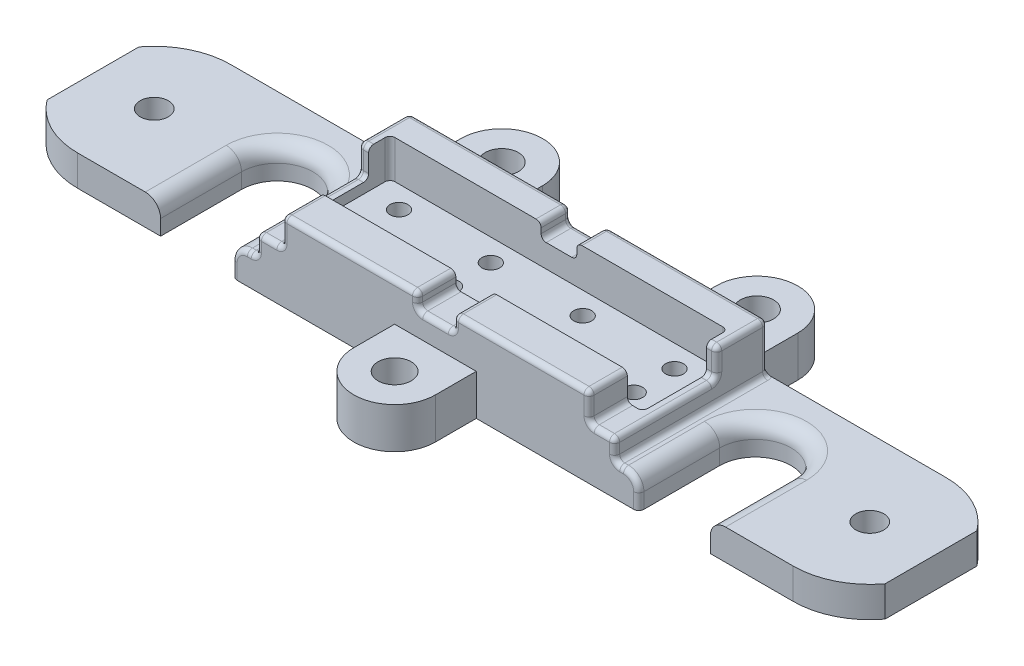
SolidWorks part; units mm, degrees
material "Delrin 2700 NC010, Low Viscosity Acetal Copolymer (SS)"
ref_plane "Front Plane" through (0, 0, 0) normal (0, 0, 1) x (1, 0, 0)
ref_plane "Top Plane" through (0, 0, 0) normal (0, 1, 0) x (1, 0, 0)
ref_plane "Right Plane" through (0, 0, 0) normal (1, 0, 0) x (0, 0, -1)
sketch "Sketch1" plane through (0, 0, 0) normal (0, 1, 0) x (1, 0, 0)
  line L1 (-35.1, -15) -> (0, -15)
  line L2 (-35.1, -15) -> (-35.1, 15)
  line L3 (-35.1, 15) -> (0, 15)
  line L4 (0, -15) -> (0, 15)
  line L5 (-35.1, -15) -> (0, 15) construction
  line L6 (-35.1, 15) -> (0, -15) construction
  point P0 (-17.55, 0)
  point P8 (0, 0)
  dimension "D1" = 35.1
  dimension "D2" = 30
extrude "Boss-Extrude1" add sketch "Sketch1" along normal blind 15.5
shell "Shell1" [suppressed] thickness 1
sketch "Sketch7" plane through (0, 15.5, 0) normal (0, 1, 0) x (1, 0, 0)
  line L0 (0, -15) -> (0, 15) construction
  line L1 (0, -7.5) -> (-33.1, -7.5)
  line L2 (0, -7.5) -> (0, 9.2)
  line L3 (0, 9.2) -> (-33.1, 9.2)
  line L4 (-33.1, -7.5) -> (-33.1, 9.2)
  line L5 (-35.1, -15) -> (0, -15) construction
  line L6 (0, 15) -> (-35.1, 15) construction
  line L7 (-35.1, 15) -> (-35.1, -15) construction
  dimension "D1" = 7.5
  dimension "D2" = 5.8
  dimension "D3" = 2
extrude "Cut-Extrude5" cut sketch "Sketch7" against normal offset from surface (7.5 mm away) 8 up to face at (-17.55, 0, 0)
sketch "Sketch2" plane through (0, 0, 0) normal (0, 1, 0) x (-1, 0, 0)
  line L0 (27, 3.15) -> (9, 3.15) construction
  line L2 (27, 3.15) -> (27, -4.85) construction
  line L3 (27, -4.85) -> (9, -4.85) construction
  line L4 (9, -4.85) -> (9, 3.15) construction
  line L5 (27, -0.85) -> (18.8977, -0.85) construction
  line L6 (17.55, -15) -> (17.55, 15) construction
  line L7 (0, 7.5) -> (0, -9.2) construction
  line L8 (27, -0.85) -> (0, -0.85) construction
  line L9 (0, -15) -> (35.1, -15) construction
  line L10 (35.1, 15) -> (0, 15) construction
  circle A0 centre (27, 3.15) radius 1.75
  circle A1 centre (9, 3.15) radius 1.75
  circle A2 centre (27, -4.85) radius 1.75
  circle A3 centre (9, -4.85) radius 1.75
  circle A5 centre (27, 3.15) radius 2.5 construction
  circle A6 centre (27, -4.85) radius 2.5 construction
  circle A7 centre (9, -4.85) radius 2.5 construction
  circle A8 centre (9, 3.15) radius 2.5 construction
  dimension "D1" = 3.5
  dimension "D4" = 9
  dimension "D5" = 5
  dimension "D2" = 18
  dimension "D3" = 8
extrude "Cut-Extrude1" cut sketch "Sketch2" along normal through all
sketch "Sketch3" [suppressed] plane through (0, 5, 0) normal (0, 1, 0) x (1, 0, 0)
  line L1 (-2.9573, -5.1559) -> (2.9865, -5.139)
  line L2 (2.9865, -5.139) -> (5.9438, 0.0169)
  line L3 (5.9438, 0.0169) -> (2.9573, 5.1559)
  line L4 (2.9573, 5.1559) -> (-2.9865, 5.139)
  line L5 (-2.9865, 5.139) -> (-5.9438, -0.0169)
  line L6 (-5.9438, -0.0169) -> (-2.9573, -5.1559)
  circle A0 centre (0, 0) radius 2.6 construction
  circle A1 centre (0, 0) radius 5.1475 construction
  dimension "D1" = 5.2
extrude "Cut-Extrude2" [suppressed] cut sketch "Sketch3" against normal blind 0.5
sketch "Sketch4" plane through (-35.1, 0, 0) normal (-1, 0, 0) x (0, 0, 1)
  line L0 (-15, 15.5) -> (15, 15.5) construction
  line L1 (-5, 15.5) -> (15, 15.5)
  line L3 (-5, 10) -> (15, 10)
  line L4 (15, 15.5) -> (15, 10)
  line L5 (0, 10) -> (0, 0) construction
  line L11 (-15, 0) -> (15, 0) construction
  line L12 (-5, 10) -> (-5, 15.5)
  dimension "D1" = 5
  dimension "D2" = 5.5
extrude "Cut-Extrude3" cut sketch "Sketch4" against normal offset from surface (5 mm away) 3 up to face at (-33.1, 11.75, -0.85) offset beyond the face yes
sketch "Sketch8" plane through (0, 0, 0) normal (0, -1, 0) x (-1, 0, 0)
  line L0 (35.1, -15) -> (70.1, -15)
  line L1 (35.1, 15) -> (70.1, 15)
  line L2 (35.1, 15) -> (35.1, -15)
  line L3 (82.1, 9) -> (82.1, -9)
  arc A0 (70.1, 15) -> (82.1, 9) centre (70.1, 0) cw
  circle A1 centre (70.1, 0) radius 2.75
  arc A2 (82.1, -9) -> (70.1, -15) centre (70.1, 0) cw
  dimension "D2" = 5.5
  dimension "D1" = 35
  dimension "D3" = 12
extrude "bolt extrude" add sketch "Sketch8" against normal blind 6
mirror "Mirror1" about plane through (0, 0, 0) normal (1, 0, 0) of bodies 112 105
fillet "Fillet3" radius 1 8 edges at (30.1, 10, 11.25) (-30.1, 10, 11.25) (30.1, 15.5, 11.25) (-30.1, 15.5, 11.25) (34.1, 15.5, -5) (34.1, 10, -5) (-34.1, 15.5, -5) (-34.1, 10, -5)
fillet "Fillet5" [suppressed] radius 0.5
sketch "Sketch9" plane through (0, 15.5, 0) normal (0, 1, 0) x (1, 0, 0)
  line L0 (35.1, 15) -> (-35.1, 15) construction
  line L1 (-3.5, 15) -> (3.5, 15)
  line L2 (-3.5, 15) -> (-3.5, -15)
  line L3 (-3.5, -15) -> (3.5, -15)
  line L4 (3.5, 15) -> (3.5, -15)
  line L5 (-29.1, -15) -> (29.1, -15) construction
  dimension "D1" = 3.5
  dimension "D2" = 3.5
extrude "Cut-Extrude6" cut sketch "Sketch9" against normal blind 3
fillet "Fillet6" radius 1 14 edges at (35.1, 10.75, -15) (-35.1, 10.75, -15) (-33.1, 9, 7.5) (-33.1, 11.75, -9.2) (33.1, 11.75, -9.2) (33.1, 9, 7.5) (-3.5, 12.5, -12.1) (3.5, 12.5, -12.1) (3.5, 12.5, 11.25) (-3.5, 12.5, 11.25) (3.5, 15.5, 11.25) (-3.5, 15.5, 11.25) (-3.5, 15.5, -12.1) (3.5, 15.5, -12.1)
fillet "Fillet7" [suppressed] radius 1
fillet "Fillet9" radius 1 25 edges at (-35.1, 10, 5.5) (35.1, 6, 0.5) (34.8071, 6, -14.7071) (35.1, 10, 5.5) (35.1, 10.2929, -4.7071) (35.1, 12.75, -5) (35.1, 15.2071, -5.2929) (35.1, 15.5, -10) (34.8071, 15.5, -14.7071) (19.3, 15.5, -15) (3.7929, 15.2071, -15) (3.5, 14, -15) (3.2071, 12.7929, -15) (0, 12.5, -15) (-3.2071, 12.7929, -15) (-3.5, 14, -15) (-3.7929, 15.2071, -15) (-19.3, 15.5, -15) (-34.8071, 15.5, -14.7071) (-35.1, 15.5, -10) (-35.1, 15.2071, -5.2929) (-35.1, 12.75, -5) (-35.1, 10.2929, -4.7071) (-34.8071, 6, -14.7071) (-35.1, 6, 0.5)
sketch "Sketch11" plane through (0, 0, 0) normal (0, -1, 0) x (1, 0, 0)
  line L0 (70.1, -15) -> (-70.1, -15) construction
  line L1 (-70.1, 15) -> (70.1, 15) construction
  line L2 (70.1, -15) -> (-70.1, -15)
  line L3 (-70.1, 15) -> (70.1, 15)
  line L4 (-70.1, 12) -> (70.1, 12)
  line L5 (70.1, -12) -> (-70.1, -12)
  line L6 (-70.1, 12) -> (-70.1, 15)
  line L7 (-70.1, -15) -> (-70.1, -12)
  line L8 (70.1, 12) -> (70.1, 15)
  line L9 (70.1, -12) -> (70.1, -15)
  point P9 (70.1, 13.5)
  dimension "D1" = 3
extrude "Boss-Extrude3" add sketch "Sketch11" along normal blind 15
sketch "Sketch12" plane through (0, 0, 0) normal (0, -1, 0) x (1, 0, 0)
  line L0 (-8, 15) -> (-8, 23)
  line L1 (17, -15) -> (17, -23)
  line L2 (8, 23) -> (8, 15)
  line L3 (8, 15) -> (-8, 15)
  line L4 (70.1, 15) -> (-70.1, 15) construction
  line L5 (-70.1, -15) -> (70.1, -15) construction
  line L6 (17, -15) -> (33, -15)
  line L7 (33, -15) -> (33, -23)
  line L8 (0, 0) -> (0, 15) construction
  line L9 (-33, -15) -> (-33, -23)
  line L10 (-17, -15) -> (-33, -15)
  line L11 (-17, -15) -> (-17, -23)
  arc A0 (-8, 23) -> (8, 23) centre (0, 23) cw
  circle A1 centre (0, 23) radius 3.25
  arc A2 (33, -23) -> (17, -23) centre (25, -23) cw
  circle A3 centre (25, -23) radius 3.25
  circle A4 centre (-25, -23) radius 3.25
  arc A5 (-33, -23) -> (-17, -23) centre (-25, -23) ccw
  point P6 (0, 15)
  dimension "D1" = 6.5
  dimension "D2" = 8
  dimension "D3" = 8
  dimension "D4" = 25
extrude "Boss-Extrude4" add sketch "Sketch12" against normal blind 8
sketch "Sketch10" plane through (0, 0, 0) normal (0, -1, 0) x (-1, 0, 0)
  line L0 (-39.85, 0.85) -> (-39.85, -15)
  line L1 (70.1, -15) -> (-70.1, -15) construction
  line L2 (-53.85, 0.85) -> (-53.85, -15)
  line L3 (39.85, 0.85) -> (39.85, -15)
  line L4 (53.85, 0.85) -> (53.85, -15)
  line L5 (-53.85, -15) -> (-39.85, -15)
  line L6 (39.85, -15) -> (53.85, -15)
  arc A0 (53.85, 0.85) -> (39.85, 0.85) centre (46.85, 0.85) ccw
  arc A1 (-39.85, 0.85) -> (-53.85, 0.85) centre (-46.85, 0.85) ccw
  dimension "D1" = 14
extrude "Cut-Extrude7" cut sketch "Sketch10" against normal through all and the other way through all
fillet "Fillet10" radius 3 6 edges at (-53.85, 6, 7.075) (-46.85, 6, -7.85) (39.85, 6, 7.075) (46.85, 6, -7.85) (-39.85, 6, 7.075) (53.85, 6, 7.075)
fillet "Fillet11" [suppressed] radius 8
fillet "Fillet12" [suppressed] radius 2
fillet "Fillet13" [suppressed] radius 2
fillet "Fillet14" radius 1 29 edges at (-39.85, -6, 15) (-38.9713, 5.1213, 15) (-36.475, 6, 15) (-35.3929, 6.2929, 15) (-35.1, 8, 15) (-34.8071, 9.7071, 15) (-32.6, 10, 15) (-30.3929, 10.2929, 15) (-30.1, 12.75, 15) (-29.8071, 15.2071, 15) (39.85, -6, 15) (38.9713, 5.1213, 15) (36.475, 6, 15) (35.3929, 6.2929, 15) (35.1, 8, 15) (34.8071, 9.7071, 15) (32.6, 10, 15) (30.3929, 10.2929, 15) (30.1, 12.75, 15) (29.8071, 15.2071, 15) (16.8, 15.5, 15) (3.7929, 15.2071, 15) (3.5, 14, 15) (3.2071, 12.7929, 15) (0, 12.5, 15) (-3.2071, 12.7929, 15) (-3.5, 14, 15) (-3.7929, 15.2071, 15) (-16.8, 15.5, 15)
sketch "Sketch13" plane through (0, 0, 0) normal (0, -1, 0) x (1, 0, 0)
  line L1 (-31, 7.15) -> (31, 7.15)
  line L2 (-31, 7.15) -> (-31, -8.85)
  line L3 (-31, -8.85) -> (31, -8.85)
  line L4 (31, 7.15) -> (31, -8.85)
  circle A0 centre (9, 3.15) radius 1.75 construction
  circle A1 centre (9, -4.85) radius 1.75 construction
  circle A2 centre (27, 3.15) radius 1.75 construction
  circle A3 centre (-27, 3.15) radius 1.75 construction
  dimension "D1" = 4
  dimension "D3" = 4
  dimension "D2" = 4
  dimension "D4" = 4
extrude "Cut-Extrude8" cut sketch "Sketch13" against normal offset from surface (4 mm away) 4 up to face at (-9, 8, 1.4)
fillet "Fillet15" radius 2 4 edges at (31, 2, -8.85) (31, 2, 7.15) (-31, 2, 7.15) (-31, 2, -8.85)
fillet "Fillet16" radius 0.5 16 edges at (-30.4142, 4, -8.2642) (0, 4, -8.85) (30.4142, 4, -8.2642) (31, 4, -0.85) (30.4142, 4, 6.5642) (0, 4, 7.15) (-30.4142, 4, 6.5642) (-30.4142, 0, 6.5642) (0, 0, 7.15) (30.4142, 0, 6.5642) (31, 0, -0.85) (30.4142, 0, -8.2642) (0, 0, -8.85) (-30.4142, 0, -8.2642) (-31, 4, -0.85) (-31, 0, -0.85)
fillet "Fillet17" [suppressed] radius 1
sketch "Sketch14" plane through (82.1, 0, 0) normal (1, 0, 0) x (0, 0, -1)
  line L1 (15, 0) -> (-15, 0)
  line L2 (15, 0) -> (15, -15)
  line L3 (15, -15) -> (-15, -15)
  line L4 (-15, 0) -> (-15, -15)
extrude "Cut-Extrude9" cut sketch "Sketch14" against normal through all
